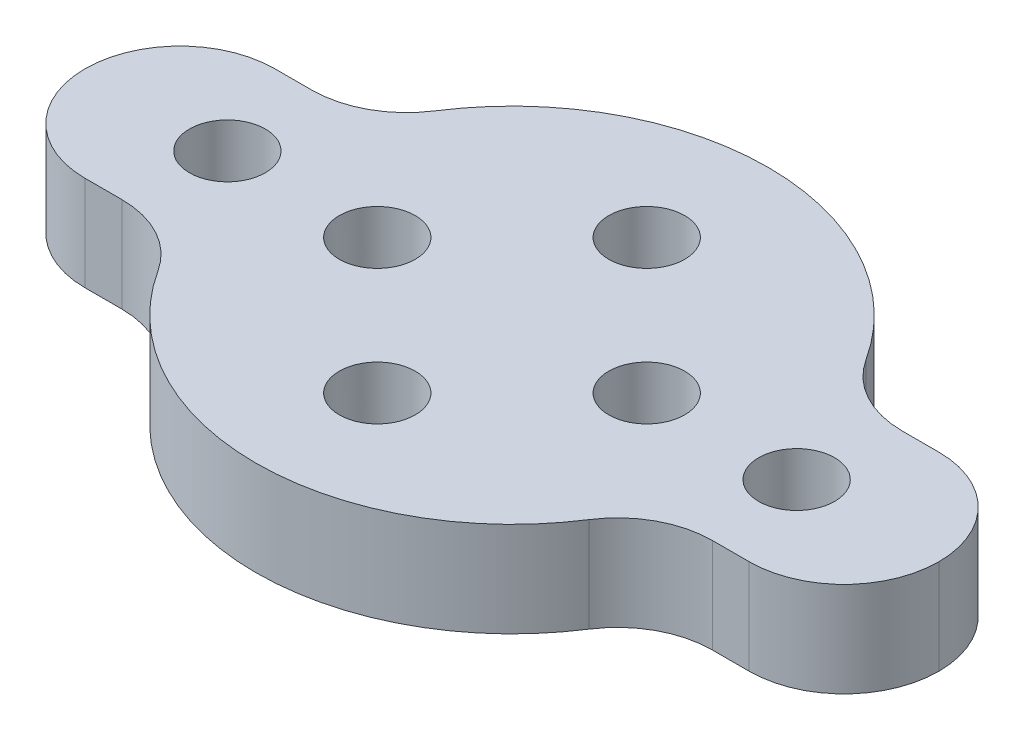
SolidWorks part; units mm, degrees
material "PLA"
ref_plane "Front" through (0, 0, 0) normal (0, 0, 1) x (1, 0, 0)
ref_plane "Top" through (0, 0, 0) normal (0, 1, 0) x (1, 0, 0)
ref_plane "Right" through (0, 0, 0) normal (1, 0, 0) x (0, 0, -1)
sketch "Sketch1" plane through (0, 0, 0) normal (0, 1, 0) x (1, 0, 0)
  line L0 (0, 0) -> (0, 12.5189) construction
  line L1 (-22.5, -5) -> (22.5, -5)
  line L2 (-22.5, -5) -> (-22.5, 5)
  line L3 (-22.5, 5) -> (22.5, 5)
  line L4 (22.5, -5) -> (22.5, 5)
  line L5 (-22.5, -5) -> (22.5, 5) construction
  line L6 (-22.5, 5) -> (22.5, -5) construction
  circle A0 centre (0, 0) radius 15 construction
  circle A1 centre (-15, 0) radius 2
  circle A2 centre (15, 0) radius 2
  circle A3 centre (-7.1, 0) radius 2
  circle A4 centre (7.1, 0) radius 2
  circle A5 centre (0, 0) radius 13.5
  circle A6 centre (0, -7.1) radius 2
  circle A7 centre (-7.1, 0) radius 2
  circle A8 centre (0, 7.1) radius 2
  point P26 (0, 0)
  dimension "D1" = 30
  dimension "D2" = 4
  dimension "D6" = 27
  dimension "D3" = 14.2
  dimension "D4" = 10
  dimension "D5" = 45
  dimension "D8" = 14.2
  dimension "D9" = 7.1
  dimension "D7" = 4
extrude "Boss-Extrude1" add sketch "Sketch1" along normal blind 5 contours L1 A5 L3 A4 A3 | A5 L1 L4 L3 A2 | L3 A5 | L1 A5 | A5 L3 L2 L1 A1 region at (-18.2282, 0, 0) region at (0, 0, 0) region at (0, 0, 5.0265) region at (18.2282, 0, 0) region at (0, 0, -13.2352)
fillet "Fillet1" radius 5 4 edges at (-22.5, 2.5, -5) (-22.5, 2.5, 5) (22.5, 2.5, 5) (22.5, 2.5, -5)
fillet "Fillet2" radius 5 4 edges at (12.5399, 2.5, -5) (-12.5399, 2.5, -5) (-12.5399, 2.5, 5) (12.5399, 2.5, 5)
sketch "Sketch3" plane through (0, 0, 0) normal (0, -1, 0) x (1, 0, 0)
  circle A0 centre (-7.1, 0) radius 3.5
  circle A1 centre (7.1, 0) radius 3.5
  dimension "D1" = 7
extrude "Cut-Extrude2" cut sketch "Sketch3" against normal blind 2
sketch "Sketch5" [suppressed] plane through (0, 5, 0) normal (0, 1, 0) x (1, 0, 0)
  circle A0 centre (0, 0) radius 10.5 construction
  dimension "D1" = 21
pattern_circular "CirPattern1" count 2 every 90 about axis through (0, 5, 0) along (0, 1, 0) of "Cut-Extrude2"
